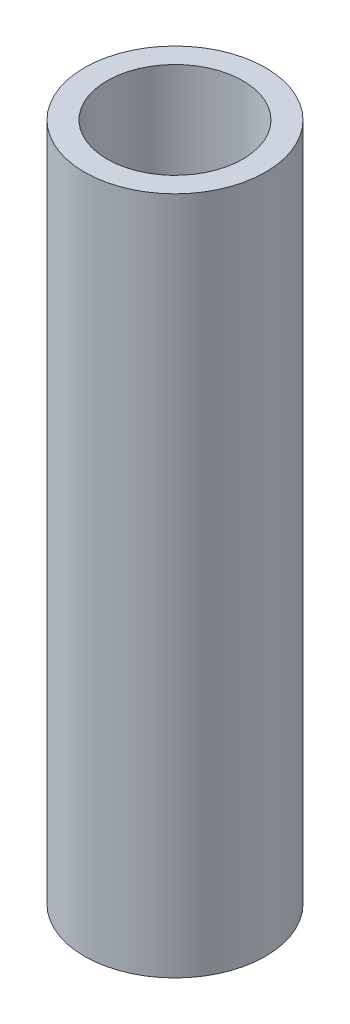
SolidWorks part; units mm, degrees
ref_plane "前视基准面" through (0, 0, 0) normal (0, 0, 1) x (1, 0, 0)
ref_plane "上视基准面" through (0, 0, 0) normal (0, 1, 0) x (1, 0, 0)
ref_plane "右视基准面" through (0, 0, 0) normal (1, 0, 0) x (0, 0, -1)
sketch "草图1" plane through (0, 0, 0) normal (0, 1, 0) x (1, 0, 0)
  circle A0 centre (0, 0) radius 6
  dimension "D1" = 12
extrude "拉伸-薄壁1" add sketch "草图1" against normal blind 60 thin thin type one direction wall 2
ref_plane "基准面4" through (0, -55, 0) normal (0, -1, 0) x (-1, 0, 0)
